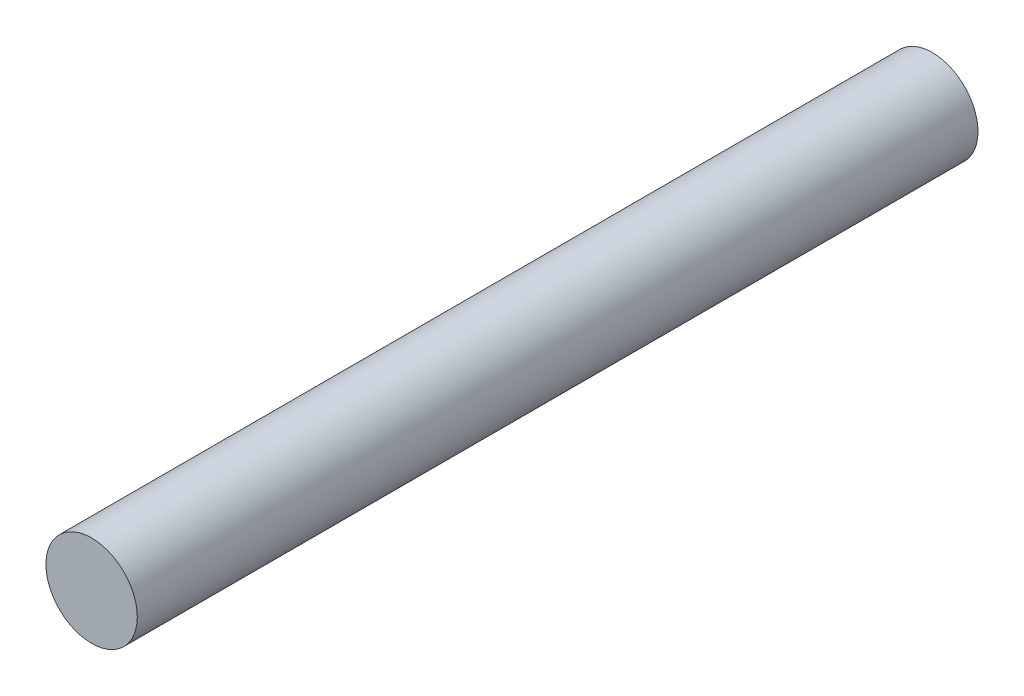
SolidWorks part; units mm, degrees
ref_plane "xy_plane" through (0, 0, 0) normal (0, 0, 1) x (1, 0, 0)
ref_plane "zx_plane" through (0, 0, 0) normal (0, 1, 0) x (1, 0, 0)
ref_plane "yz_plane" through (0, 0, 0) normal (1, 0, 0) x (0, 0, -1)
ref_axis "x_axis" through (-80.9, 0, 0) along (1, 0, 0)
ref_axis "y_axis" through (0, -50, 0) along (0, 1, 0)
ref_axis "z_axis" through (0, 0, -80.9) along (0, 0, 1)
sketch "pivotShaft_sketch" plane through (0, 0, 0) normal (0, 0, 1) x (1, 0, 0)
  circle A0 centre (0, 0) radius 2.5
extrude "pivotShaft_extrude" add sketch "pivotShaft_sketch" along normal mid plane 46
equation "\"D1@pivotShaft_sketch\"=\"externalParameters.this.diameter\""
equation "\"D1@pivotShaft_extrude\"=\"externalParameters.this.length\""
